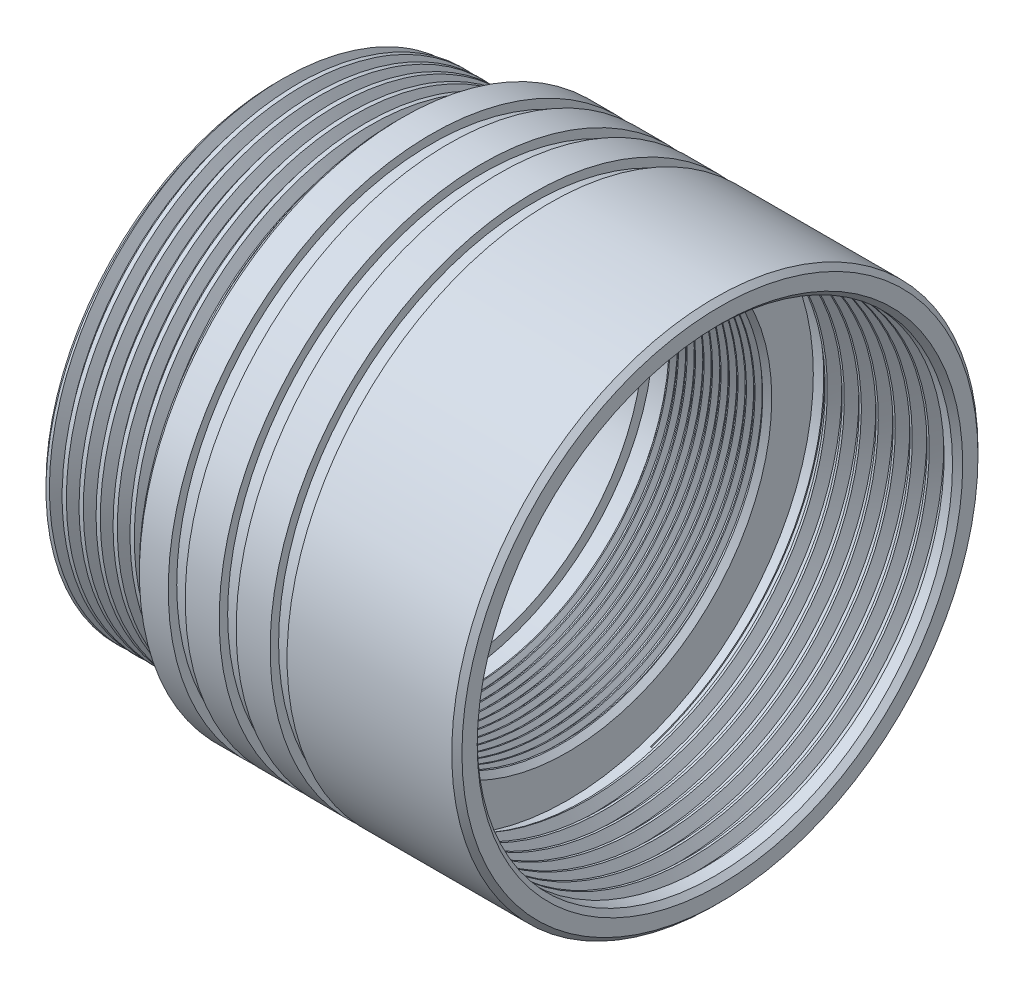
SolidWorks part; units mm, degrees
material "3.1325 (EN-AW 2017A)"
ref_plane "Front Plane" through (0, 0, 0) normal (0, 0, 1) x (1, 0, 0)
ref_plane "Top Plane" through (0, 0, 0) normal (0, 1, 0) x (1, 0, 0)
ref_plane "Right Plane" through (0, 0, 0) normal (1, 0, 0) x (0, 0, -1)
sketch "Sketch1" plane through (0, 0, 0) normal (0, 0, 1) x (1, 0, 0)
  line L0 (39.69, 0) -> (-39.69, 0) construction
  line L1 (0, -12.05) -> (0, -13.7)
  line L3 (7, -13.5) -> (7, -15.2)
  line L4 (7.3, -15.5) -> (9, -15.5)
  line L5 (26, -15.2) -> (26, -14.3)
  line L7 (17, -14.5) -> (17, -12.05)
  line L8 (16.7, -11.75) -> (11, -11.75)
  line L9 (2, -11.5) -> (2, -10.25)
  line L10 (2, -10.25) -> (1.8, -10.25)
  line L11 (0.3, -14) -> (6, -14)
  line L12 (6, -14) -> (6, -13.5)
  line L13 (6, -13.5) -> (7, -13.5)
  line L14 (1.8, -10.25) -> (0, -12.05)
  line L15 (0, -13.7) -> (0.3, -14)
  line L16 (7, -15.2) -> (7.3, -15.5)
  line L17 (25.7, -15.5) -> (26, -15.2)
  line L18 (17, -12.05) -> (16.7, -11.75)
  line L19 (26, -14.3) -> (25.7, -14)
  line L20 (9, -15.5) -> (9, -15)
  line L21 (9, -15) -> (10, -15)
  line L22 (10, -15) -> (10, -15.5)
  line L23 (12, -15.5) -> (12, -15)
  line L24 (12, -15) -> (13, -15)
  line L25 (13, -15) -> (13, -15.5)
  line L26 (15, -15.5) -> (15, -15)
  line L27 (15, -15) -> (16, -15)
  line L28 (16, -15) -> (16, -15.5)
  line L29 (10, -15.5) -> (12, -15.5)
  line L30 (13, -15.5) -> (15, -15.5)
  line L31 (16, -15.5) -> (25.7, -15.5)
  line L32 (11, -11.75) -> (11, -12.1)
  line L34 (11, -12.1) -> (10, -12.1)
  line L35 (10, -12.1) -> (10, -11.5)
  line L36 (10, -11.5) -> (2, -11.5)
  line L37 (25.7, -14) -> (18, -14)
  line L38 (18, -14) -> (18, -14.5)
  line L39 (18, -14.5) -> (17, -14.5)
  point P0 (0, -10.25)
  point P4 (0, 0)
  point P6 (0, -14)
  point P9 (7, -15.5)
  point P10 (26, -15.5)
  point P11 (26, -14)
  point P13 (17, -11.75)
  dimension "D1" = 26
  dimension "D2" = 31
  dimension "D3" = 28
  dimension "D4" = 7
  dimension "D5" = 0.5
  dimension "D6" = 6
  dimension "D7" = 28
  dimension "D8" = 23.5
  dimension "D9" = 9
  dimension "D10" = 20.5
  dimension "D11" = 2
  dimension "D12" = 1
  dimension "D13" = 0.5
  dimension "D20" = 2
  dimension "D22" = 3
  dimension "D23" = 23
  dimension "D24" = 6
  dimension "D25" = 0.35
  dimension "D26" = 1
  dimension "D27" = 0.5
  dimension "D28" = 1
  dimension "D18" = 0.3
  dimension "D21" = 3
revolve "Revolve1" add sketch "Sketch1" angle 360 about L0
cosmetic thread "Cosmetic Thread1" parameters "D2"=27
cosmetic thread "Cosmetic Thread2" parameters "D2"=29
cosmetic thread "Cosmetic Thread3" parameters "D2"=24
thread "Thread1" pitch 1 method cut profile "Thread Profile2" start angle 0, offset 0, length 0, pitch 1, diameter 28
ref_plane "Plane2" through (0, 0, -14) normal (0, -1, 0) x (0, 0, -1)
sketch "Thread Profile2" plane through (0, 0, -14) normal (0, -1, 0) x (0, 0, -1)
  line L0 (0, 0) -> (0, 1) construction
  line L1 (0, 0.75) -> (-0.5413, 0.4375)
  line L2 (-0.5413, 0.4375) -> (-0.5413, 0.3125)
  line L3 (-0.5413, 0.3125) -> (0, 0)
  line L4 (-0.5413, 0.375) -> (0, 0.375) construction
  line L11 (0, 0.75) -> (0, 0)
  point P6 (0, 0)
  dimension "Pitch" = 1
  dimension "Profile_Angle" = 60
  dimension "Profile_Land" = 0.125
  dimension "Profile_Height" = 0.5413
thread "Thread2" pitch 1 method cut profile "Thread Profile3" start angle 0, offset 0, length 0, pitch 1, diameter 28
ref_plane "Plane3" through (25.7, 0, 14) normal (0, -1, 0) x (0, 0, 1)
sketch "Thread Profile3" plane through (25.7, 0, 14) normal (0, -1, 0) x (0, 0, 1)
  line L0 (0, 0) -> (0, 1) construction
  line L11 (0, 0.875) -> (0, 0)
  line L12 (0, 0) -> (0.5413, 0.3125)
  line L13 (0.5413, 0.3125) -> (0.5413, 0.5625)
  line L15 (0.5413, 0.5625) -> (0, 0.875)
  line L17 (0.5413, 0.4375) -> (0, 0.4375) construction
  point P3 (0, 0)
  dimension "Pitch" = 1
  dimension "Profile_Angle" = 60
  dimension "Profile_Land" = 0.25
  dimension "Profile_Height" = 0.5413
thread "Thread3" pitch 0.5 method cut profile "Thread Profile5" start angle 0, offset 0, length 0, pitch 0.5, diameter 23.5
ref_plane "Plane5" through (17, 0, 11.75) normal (0, -1, 0) x (0, 0, 1)
sketch "Thread Profile5" plane through (17, 0, 11.75) normal (0, -1, 0) x (0, 0, 1)
  line L0 (0, 0) -> (0, 0.5) construction
  line L11 (0, 0.4375) -> (0, 0)
  line L12 (0, 0) -> (0.2706, 0.1563)
  line L13 (0.2706, 0.1563) -> (0.2706, 0.2813)
  line L15 (0.2706, 0.2813) -> (0, 0.4375)
  line L17 (0.2706, 0.2188) -> (0, 0.2188) construction
  point P3 (0, 0)
  dimension "Pitch" = 0.5
  dimension "Profile_Angle" = 60
  dimension "Profile_Land" = 0.125
  dimension "Profile_Height" = 0.2706
ref_axis "Axis1" through (2, 0, 0) along (1, 0, 0)
